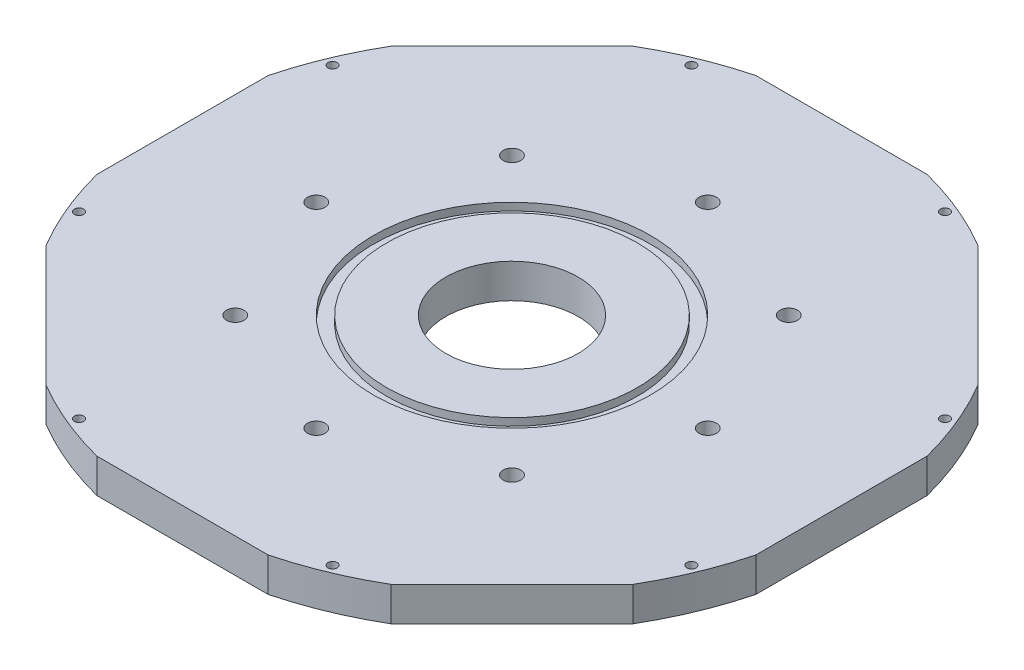
SolidWorks part; units mm, degrees
other "Markup1"
sketch "Sketch46" plane through (-122.3, 0, 122.3) normal (-0.1263, -0.9546, 0.2699) x (-0.172, -0.2469, -0.9537)
material "6061-T6 (SS)"
ref_plane "Front Plane" through (0, 0, 0) normal (0, 0, 1) x (1, 0, 0)
ref_plane "Top Plane" through (0, 0, 0) normal (0, 1, 0) x (1, 0, 0)
ref_plane "Right Plane" through (0, 0, 0) normal (1, 0, 0) x (0, 0, -1)
sketch "Sketch1" plane through (0, 0, 0) normal (0, 1, 0) x (1, 0, 0)
  line L1 (-50.6583, 122.3) -> (-122.3, 50.6583)
  line L2 (-122.3, 50.6583) -> (-122.3, -50.6583)
  line L3 (-122.3, -50.6583) -> (-50.6583, -122.3)
  line L4 (-50.6583, -122.3) -> (50.6583, -122.3)
  line L5 (50.6583, -122.3) -> (122.3, -50.6583)
  line L6 (122.3, -50.6583) -> (122.3, 50.6583)
  line L7 (122.3, 50.6583) -> (50.6583, 122.3)
  line L8 (50.6583, 122.3) -> (-50.6583, 122.3)
  circle A0 centre (0, 0) radius 122.3 construction
  circle A1 centre (0, 0) radius 126.365
  dimension "D2" = 252.73
  dimension "D1" = 244.6
extrude "Boss-Extrude1" add sketch "Sketch1" along normal blind 12.7 contours L4 A1 L5 L6 L7 L8 L1 L2 L3 region at (0, 0, 0)
sketch "Sketch3" plane through (0, 12.7, 0) normal (0, 1, 0) x (1, 0, 0)
  circle A0 centre (0, 0) radius 24.5745
  dimension "D1" = 49.149
extrude "Cut-Extrude1" cut sketch "Sketch3" against normal through all contours A0
sketch "Sketch5" plane through (0, 12.7, 0) normal (0, 1, 0) x (1, 0, 0)
  circle A0 centre (0, 0) radius 46.5455
  circle A1 centre (0, 0) radius 51.3715
  dimension "D1" = 93.091
  dimension "D2" = 102.743
extrude "Cut-Extrude2" cut sketch "Sketch5" against normal blind 2.794
sketch "Sketch19" plane through (0, 12.7, 0) normal (0, 1, 0) x (1, 0, 0)
  line L5 (-63.9978, 108.9605) -> (-31.7934, 122.3) construction
  line L6 (-47.8956, 115.6303) -> (-43.6974, 105.4949) construction
  circle A4 centre (0, 0) radius 122.9995
  circle A5 centre (-47.0699, 113.6367) radius 2.2479
  dimension "D1" = 4.4958
  dimension "D3" = 245.999
sketch "Sketch21" plane through (0, 12.7, 0) normal (0, 1, 0) x (1, 0, 0)
  point P0 (-72.644, 0)
  dimension "D1" = 72.644
hole_wizard "5/16-18 Tapped Hole1" positions "Sketch22" profile "Sketch23" tap size "5/16-18" standard "ANSI Inch"
sketch "Sketch22" plane through (0, 12.7, 0) normal (0, 1, 0) x (1, 0, 0)
  point P0 (-72.644, 0)
sketch "Sketch23" plane through (-72.644, 12.7, 0) normal (1, 0, 0) x (0, 0, 1)
  line L0 (0, 0) -> (0, 8.3111)
  line L1 (0, 8.3111) -> (3.2639, 6.35)
  line L2 (3.2639, 6.35) -> (3.2639, 0)
  line L5 (3.2639, 0) -> (0, 0)
  line L10 (0, 8.3111) -> (-3.2639, 6.35) construction
  line L11 (0, -6.35) -> (0, 107.95) construction
  dimension "Tap Drill Dia." = 6.5278
  dimension "Tap Drill Depth" = 6.35
  dimension "Drill Angle" = 118
cosmetic thread "Hole Thread2" parameters "D1"=6.35, "D2"=7.9375
sketch "Sketch33" [suppressed] plane through (0, 19.05, 0) normal (0, 1, 0) x (1, 0, 0)
  circle A0 centre (-71.374, 0) radius 3.9687
  dimension "D1" = 7.9375
sketch "Sketch37" plane through (0, 0, 0) normal (0, -1, 0) x (1, 0, 0)
  circle A0 centre (0, 0) radius 119.0625
  circle A1 centre (0, 0) radius 115.2525
  dimension "D1" = 238.125
  dimension "D2" = 230.505
extrude "Cut-Extrude7" cut sketch "Sketch37" against normal blind 2.667
pattern_circular "CirPattern4" count 8 over 360 about axis through (0, 0, 0) along (0, 1, 0) of "5/16-18 Tapped Hole1" reverse direction yes
cosmetic thread "Hole Thread3" parameters "D1"=6.35, "D2"=7.9375
cosmetic thread "Hole Thread4" parameters "D1"=6.35, "D2"=7.9375
cosmetic thread "Hole Thread5" parameters "D1"=6.35, "D2"=7.9375
cosmetic thread "Hole Thread6" parameters "D1"=6.35, "D2"=7.9375
cosmetic thread "Hole Thread7" parameters "D1"=6.35, "D2"=7.9375
cosmetic thread "Hole Thread8" parameters "D1"=6.35, "D2"=7.9375
cosmetic thread "Hole Thread9" parameters "D1"=6.35, "D2"=7.9375
hole_wizard "#8-32 Tapped Hole1" positions "Sketch47" profile "Sketch49" tap size "#8-32" standard "ANSI Inch" end condition through all
sketch "Sketch47" plane through (0, 12.7, 0) normal (0, 1, 0) x (1, 0, 0)
  point P0 (-47.0699, 113.6367)
sketch "Sketch49" plane through (-47.0699, 12.7, -113.6367) normal (1, 0, 0) x (0, 0, 1)
  line L0 (0, 0) -> (0, 12.7)
  line L1 (0, 12.7) -> (1.7272, 12.7)
  line L2 (1.7272, 12.7) -> (1.7272, 0)
  line L5 (1.7272, 0) -> (0, 0)
  line L11 (0, -6.35) -> (0, 107.95) construction
  dimension "Thru Tap Drill Dia." = 3.4544
  dimension "Thru Tap Drill Depth" = 12.7
cosmetic thread "Hole Thread10" parameters "D2"=4.1656
pattern_circular "CirPattern5" count 8 over 360 about axis through (0, 0, 0) along (0, 1, 0) of "#8-32 Tapped Hole1"
cosmetic thread "Hole Thread11" parameters "D2"=4.1656
cosmetic thread "Hole Thread12" parameters "D2"=4.1656
cosmetic thread "Hole Thread13" parameters "D2"=4.1656
cosmetic thread "Hole Thread14" parameters "D2"=4.1656
cosmetic thread "Hole Thread15" parameters "D2"=4.1656
cosmetic thread "Hole Thread16" parameters "D2"=4.1656
cosmetic thread "Hole Thread17" parameters "D2"=4.1656
